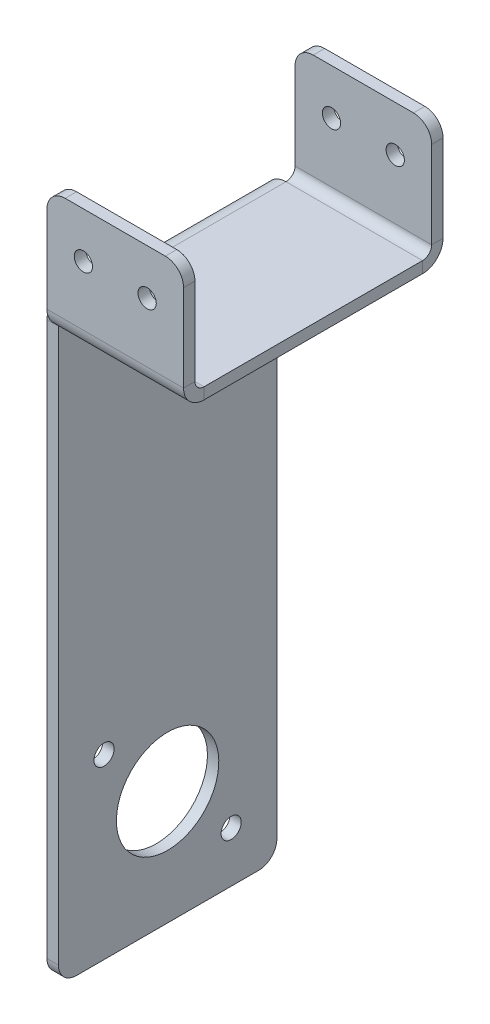
SolidWorks part; units mm, degrees
note: The reader was unsure of these and kept them because the rebuilt part matched: thickness of "Base-Flange1", "Edge-Flange1", "Edge-Flange2", "Sheet-Metal1", "Sheet-Metal2", "Sheet-Metal3", "Sheet-Metal4", "Sheet-Metal5"; flange length of "Edge-Flange1", "Edge-Flange2".
ref_plane "Front Plane" through (0, 0, 0) normal (0, 0, 1) x (1, 0, 0)
ref_plane "Top Plane" through (0, 0, 0) normal (0, 1, 0) x (1, 0, 0)
ref_plane "Right Plane" through (0, 0, 0) normal (1, 0, 0) x (0, 0, -1)
sketch "Sketch1" plane through (0, 0, 0) normal (0, 1, 0) x (1, 0, 0)
  line L1 (-19.05, -30.48) -> (19.05, -30.48)
  line L2 (-19.05, -30.48) -> (-19.05, 30.48)
  line L3 (-19.05, 30.48) -> (19.05, 30.48)
  line L4 (19.05, -30.48) -> (19.05, 30.48)
  line L5 (-19.05, -30.48) -> (19.05, 30.48) construction
  line L6 (-19.05, 30.48) -> (19.05, -30.48) construction
  point P1 (0, 0)
  dimension "D1" = 38.1
  dimension "D2" = 60.96
base flange "Base-Flange1" sketch "Sketch1" thickness 3.175 reverse thickness direction no parameters "D1"=2.54
edge flange "Edge-Flange1" sketch "Sketch10" flange profiles "Sketch10", "Sketch11" flange angle 90 flange length 35.052 flange position bend outside bend radius 2.54 thickness 3.175 relief rectangular parameters "D6"=10, "D8"=0.254
sketch "Sketch10" plane through (0, 0, 30.48) normal (0, 0, 1) x (1, 0, 0)
  line L0 (-19.05, 0) -> (19.05, 0) construction
  line L1 (-19.05, 0) -> (19.05, 0)
  line L2 (-19.05, 0) -> (-19.05, 31.877)
  line L3 (-19.05, 31.877) -> (19.05, 31.877)
  line L4 (19.05, 31.877) -> (19.05, 0)
sketch "Sketch11" plane through (0, 0, -30.48) normal (0, 0, -1) x (-1, 0, 0)
  line L0 (-19.05, 0) -> (19.05, 0) construction
  line L1 (-19.05, 0) -> (19.05, 0)
  line L2 (-19.05, 0) -> (-19.05, 31.877)
  line L3 (-19.05, 31.877) -> (19.05, 31.877)
  line L4 (19.05, 31.877) -> (19.05, 0)
bend "EdgeBend1" bend radius 2.54 bend angle 90 parameters "D5"=1
bend "EdgeBend2" bend radius 2.54 bend angle 90 parameters "D5"=2
edge flange "Edge-Flange2" sketch "Sketch16" flange angle 90 flange length 165.1 flange position bend outside bend radius 2.54 thickness 3.175 relief rectangular parameters "D6"=10
sketch "Sketch16" plane through (-19.05, -3.175, 0) normal (-1, 0, 0) x (0, 0, -1)
  line L0 (30.48, 0) -> (-30.48, 0) construction
  line L1 (30.48, 0) -> (-30.48, 0)
  line L2 (-30.48, 0) -> (-30.48, 161.925)
  line L3 (-30.48, 161.925) -> (30.48, 161.925)
  line L4 (30.48, 161.925) -> (30.48, 0)
bend "EdgeBend3" bend radius 2.54 bend angle 90 parameters "D5"=3
sketch "Sketch17" plane through (-24.765, 0, 0) normal (-1, 0, 0) x (0, 0, 1)
  line L0 (-30.48, -165.1) -> (30.48, -165.1) construction
  line L1 (30.48, -165.1) -> (30.48, -5.715) construction
  line L3 (17.7292, -115.5446) -> (-17.7292, -151.003)
  circle A0 centre (0, -133.2738) radius 14.2812
  circle A4 centre (-17.7292, -151.003) radius 2.8067
  circle A5 centre (17.7292, -115.5446) radius 2.8067
  circle A6 centre (0, -133.2738) radius 25.0729 construction
  dimension "D1" = 28.5623
  dimension "D7" = 5.6134
  dimension "D8" = 5.6134
  dimension "D2" = 31.8262
  dimension "D6" = 30.48
  dimension "D4" = 35.4584
  dimension "D5" = 35.4584
extrude "Cut-Extrude1" cut sketch "Sketch17" against normal through all contours A0 | A5 | A4 normal cut yes
sketch "Sketch18" plane through (0, 0, 36.195) normal (0, 0, 1) x (1, 0, 0)
  line L0 (19.05, 31.877) -> (-19.05, 31.877) construction
  line L1 (19.05, 2.54) -> (19.05, 31.877) construction
  line L2 (-19.05, 31.877) -> (-19.05, 2.54) construction
  circle A0 centre (8.89, 19.177) radius 2.5527
  circle A1 centre (-8.89, 19.177) radius 2.5527
  dimension "D1" = 5.1054
  dimension "D2" = 5.1054
  dimension "D3" = 12.7
  dimension "D4" = 12.7
  dimension "D5" = 10.16
  dimension "D6" = 10.16
extrude "Cut-Extrude2" cut sketch "Sketch18" against normal through all normal cut yes
fillet "Fillet1" radius 5.08 6 edges at (19.05, 31.877, 34.6075) (-19.05, 31.877, 34.6075) (-19.05, 31.877, -34.6075) (19.05, 31.877, -34.6075) (-23.1775, -165.1, -30.48) (-23.1775, -165.1, 30.48)
sketch "Bend-Lines1" [suppressed] plane through (0, 0, 0) normal (0, 1, 0) x (1, 0, 0)
sketch "Bounding-Box1" [suppressed] plane through (0, 0, 0) normal (0, 1, 0) x (1, 0, 0)
sheet metal parameters "Sheet-Metal1" thickness 3.175 parameters "D1"=2.54
flat pattern "Flat-Pattern1" [suppressed]
sketch "Bend-Lines2" plane through (0, 0, 0) normal (0, 1, 0) x (1, 0, 0)
sketch3d "Bounding-Box2" [suppressed]
  line L0 (-38.1, 25.4, 0) -> (38.1, 25.4, 0) construction
  line L1 (-38.1, -25.4, 0) -> (38.1, -25.4, 0) construction
  line L2 (-38.1, 25.4, 0) -> (-38.1, -25.4, 0) construction
  line L3 (38.1, 25.4, 0) -> (38.1, -25.4, 0) construction
sheet metal parameters "Sheet-Metal2" thickness 3.175 parameters "D1"=2.54, "D7"=1.6129
flat pattern "Flat-Pattern1"
sketch "Bend-Lines2" plane through (0, 0, 0) normal (0, 1, 0) x (1, 0, 0)
  line L0 (19.05, 27.94) -> (-19.05, 27.94) construction
  line L1 (-19.05, -27.94) -> (19.05, -27.94) construction
  line L2 (19.05, 27.94) -> (-19.05, 27.94) construction
  line L3 (-19.05, -27.94) -> (19.05, -27.94) construction
sketch3d "Bounding-Box2" [suppressed]
  line L0 (-19.05, -61.3791, 0) -> (-19.05, 61.3791, 0) construction
  line L1 (19.05, -61.3791, 0) -> (19.05, 61.3791, 0) construction
  line L2 (-19.05, -61.3791, 0) -> (19.05, -61.3791, 0) construction
  line L3 (-19.05, 61.3791, 0) -> (19.05, 61.3791, 0) construction
bend of the flat pattern "Flatten-<EdgeBend1>1"
bend of the flat pattern "Flatten-<EdgeBend2>1"
sheet metal parameters "Sheet-Metal3" thickness 3.175 parameters "D1"=2.54, "D7"=1.6129
flat pattern "Flat-Pattern1"
sketch "Bend-Lines2" plane through (0, 0, 0) normal (0, 1, 0) x (1, 0, 0)
  line L0 (19.05, 27.94) -> (-19.05, 27.94) construction
  line L1 (-19.05, -27.94) -> (19.05, -27.94) construction
  line L2 (19.05, 27.94) -> (-19.05, 27.94) construction
  line L3 (-19.05, -27.94) -> (19.05, -27.94) construction
  line L4 (-21.59, 25.4) -> (-21.59, -25.4) construction
  line L5 (-21.59, 25.4) -> (-21.59, -25.4) construction
sketch3d "Bounding-Box2" [suppressed]
  line L0 (19.05, 61.3791, 0) -> (-134.2771, 61.3791, 0) construction
  line L1 (19.05, -61.3791, 0) -> (-134.2771, -61.3791, 0) construction
  line L2 (19.05, 61.3791, 0) -> (19.05, -61.3791, 0) construction
  line L3 (-134.2771, 61.3791, 0) -> (-134.2771, -61.3791, 0) construction
bend of the flat pattern "Flatten-<EdgeBend1>1"
bend of the flat pattern "Flatten-<EdgeBend2>1"
bend of the flat pattern "Flatten-<EdgeBend3>1"
sheet metal parameters "Sheet-Metal4" thickness 3.175 parameters "D1"=2.54, "D7"=1.6129
flat pattern "Flat-Pattern1"
sketch "Bend-Lines2" plane through (0, 0, 0) normal (0, 1, 0) x (1, 0, 0)
  line L0 (19.05, 33.02) -> (-19.05, 33.02) construction
  line L1 (-19.05, -33.02) -> (19.05, -33.02) construction
  line L2 (19.05, 33.02) -> (-19.05, 33.02) construction
  line L3 (-19.05, -33.02) -> (19.05, -33.02) construction
  line L4 (-21.59, 30.48) -> (-21.59, -30.48) construction
  line L5 (-21.59, 30.48) -> (-21.59, -30.48) construction
sketch3d "Bounding-Box2" [suppressed]
  line L0 (19.05, 64.77, 0) -> (-132.588, 64.77, 0) construction
  line L1 (19.05, -64.77, 0) -> (-132.588, -64.77, 0) construction
  line L2 (19.05, 64.77, 0) -> (19.05, -64.77, 0) construction
  line L3 (-132.588, 64.77, 0) -> (-132.588, -64.77, 0) construction
bend of the flat pattern "Flatten-<EdgeBend1>1"
bend of the flat pattern "Flatten-<EdgeBend2>1"
bend of the flat pattern "Flatten-<EdgeBend3>1"
sheet metal parameters "Sheet-Metal5" thickness 3.175 parameters "D1"=2.54, "D7"=1.6129
flat pattern "Flat-Pattern1"
sketch "Bend-Lines2" plane through (0, 0, 0) normal (0, 1, 0) x (1, 0, 0)
  line L0 (19.05, 33.02) -> (-19.05, 33.02) construction
  line L1 (-19.05, -33.02) -> (19.05, -33.02) construction
  line L2 (19.05, 33.02) -> (-19.05, 33.02) construction
  line L3 (-19.05, -33.02) -> (19.05, -33.02) construction
  line L4 (-21.59, 30.48) -> (-21.59, -30.48) construction
  line L5 (-21.59, 30.48) -> (-21.59, -30.48) construction
sketch3d "Bounding-Box2" [suppressed]
  line L0 (-183.515, 64.8969, 0) -> (19.05, 64.897, 0) construction
  line L1 (-183.515, -64.8971, 0) -> (19.0501, -64.897, 0) construction
  line L2 (-183.515, 64.8969, 0) -> (-183.515, -64.8971, 0) construction
  line L3 (19.05, 64.897, 0) -> (19.0501, -64.897, 0) construction
bend of the flat pattern "Flatten-<EdgeBend1>1"
bend of the flat pattern "Flatten-<EdgeBend2>1"
bend of the flat pattern "Flatten-<EdgeBend3>1"
equation "\"D2@Sketch18\"=\"D1@Sketch18\""
equation "\"D8@Sketch17\"=\"D7@Sketch17\""
